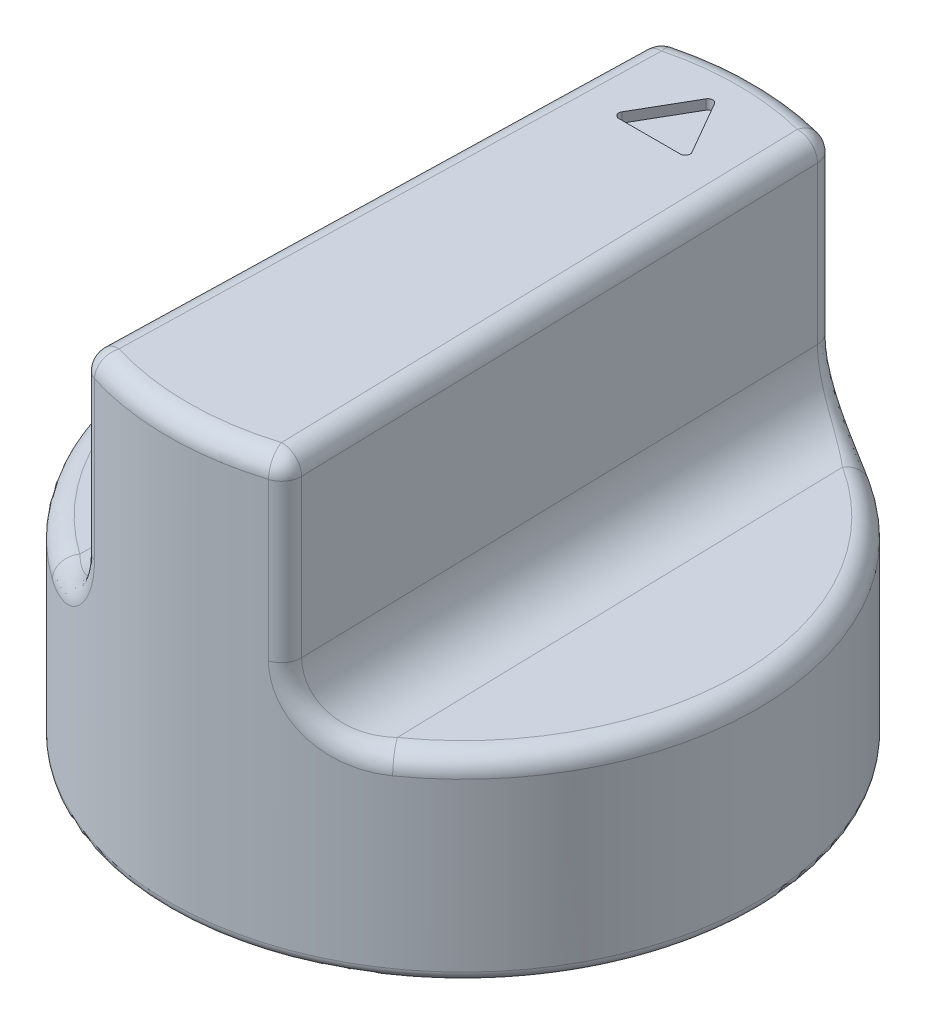
SolidWorks part; units mm, degrees
ref_plane "Front Plane" through (0, 0, 0) normal (0, 0, 1) x (1, 0, 0)
ref_plane "Top Plane" through (0, 0, 0) normal (0, 1, 0) x (1, 0, 0)
ref_plane "Right Plane" through (0, 0, 0) normal (1, 0, 0) x (0, 0, -1)
sketch "Sketch1" plane through (0, 0, 0) normal (0, 1, 0) x (1, 0, 0)
  line L0 (0, 15) -> (0, -15)
  arc A0 (0, -15) -> (0, 15) centre (0, 0) ccw
  dimension "D1" = 30
extrude "Boss-Extrude1" add sketch "Sketch1" along normal blind 10
sketch "Sketch2" plane through (0, 10, 0) normal (0, 1, 0) x (1, 0, 0)
  line L0 (0, 15) -> (0, -15)
  arc A0 (0, -15) -> (0, 15) centre (0, 0) ccw
extrude "Boss-Extrude2" add sketch "Sketch2" along normal blind 12
sketch "Sketch4" plane through (0, 22, 0) normal (0, 1, 0) x (1, 0, 0)
  line L0 (4.4356, 14.3292) -> (5.1535, -14.0869)
  arc A0 (0, 15) -> (4.4356, 14.3292) centre (-0.2282, -1.5091) cw construction
  arc A1 (0, -15) -> (0, 15) centre (0, 0) ccw construction
  arc A2 (0, -15) -> (5.1535, -14.0869) centre (-0.7526, 4.2478) ccw construction
  arc A3 (4.4356, 14.3292) -> (5.1535, -14.0869) centre (0, 0) cw
  arc M4 (0, -15) -> (0, 15) centre (0, 0) ccw
  dimension "D1" = 4.5
  dimension "D2" = 4.7961
  dimension "D3" = 5.25
  dimension "D4" = 28.4161
extrude "Cut-Extrude1" cut sketch "Sketch4" against normal blind 12 contours L0 M4 region at (9.0236, 22, -0.228)
mirror "Mirror1" about plane through (0, 10, -15) normal (1, 0, 0) of bodies 105
fillet "Fillet1" radius 3 2 edges at (-4.7946, 10, -0.1211) (4.7946, 10, -0.1211)
sketch "Sketch5" plane through (0, 22, 0) normal (0, 1, 0) x (1, 0, 0)
  line L0 (1.567, 9.5) -> (-1.567, 9.5)
  line L1 (-1.7835, 9.875) -> (-0.2165, 12.5891)
  line L2 (0.2165, 12.5891) -> (1.7835, 9.875)
  arc A0 (1.567, 9.5) -> (1.7835, 9.875) centre (1.567, 9.75) ccw
  arc A1 (-1.567, 9.5) -> (-1.7835, 9.875) centre (-1.567, 9.75) cw
  arc A2 (0.2165, 12.5891) -> (-0.2165, 12.5891) centre (0, 12.4641) ccw
  point P6 (2, 9.5)
  point P9 (-2, 9.5)
  dimension "D6" = 0.25
  dimension "D1" = 4
  dimension "D2" = 60
  dimension "D3" = 60
  dimension "D4" = 2
  dimension "D5" = 9.5
extrude "Cut-Extrude2" cut sketch "Sketch5" against normal blind 0.5
sketch "Sketch6" plane through (0, 0, 0) normal (0, -1, 0) x (1, 0, 0)
  line L0 (0, 0) -> (0, -4.5) construction
  line L6 (-1, -3.3541) -> (-1, -4.5)
  line L7 (-1, -4.5) -> (1, -4.5)
  line L8 (1, -3.3541) -> (1, -4.5)
  arc A1 (1, -3.3541) -> (-1, -3.3541) centre (0, 0) ccw
  point P5 (0, 0)
  dimension "D1" = 7
  dimension "D2" = 4.5
  dimension "D3" = 2
extrude "Cut-Extrude3" cut sketch "Sketch6" against normal blind 5
fillet "Fillet5" radius 0.5 1 edges at (0, 0, 15)
sketch "Sketch8" plane through (0, 22, 0) normal (0, 1, 0) x (1, 0, 0)
  arc A0 (-4.4356, 14.3292) -> (4.43, 14.3309) centre (0, 0) cw construction
  arc A1 (7.47, 13.0077) -> (4.4356, 14.3292) centre (0, 0) ccw construction
  arc A2 (-5.1535, -14.0869) -> (5.1334, -14.0943) centre (0, 0) ccw construction
  dimension "D1" = 9
  dimension "D2" = 10.5
  dimension "D3" = 15
fillet "Fillet6" radius 1 14 edges at (-4.4356, 17.5, -14.3292) (-5.4283, 10.7787, -13.9833) (-14.9952, 10, -0.3788) (-5.7385, 11.2127, 13.8589) (-5.1535, 17.5, 14.0869) (0, 22, 15) (5.1535, 17.5, 14.0869) (6.1274, 10.7787, 13.6914) (14.9952, 10, -0.3788) (5.0314, 11.2127, -14.131) (4.4356, 17.5, -14.3292) (0, 22, -15) (4.7946, 22, -0.1211) (-4.7946, 22, -0.1211)
